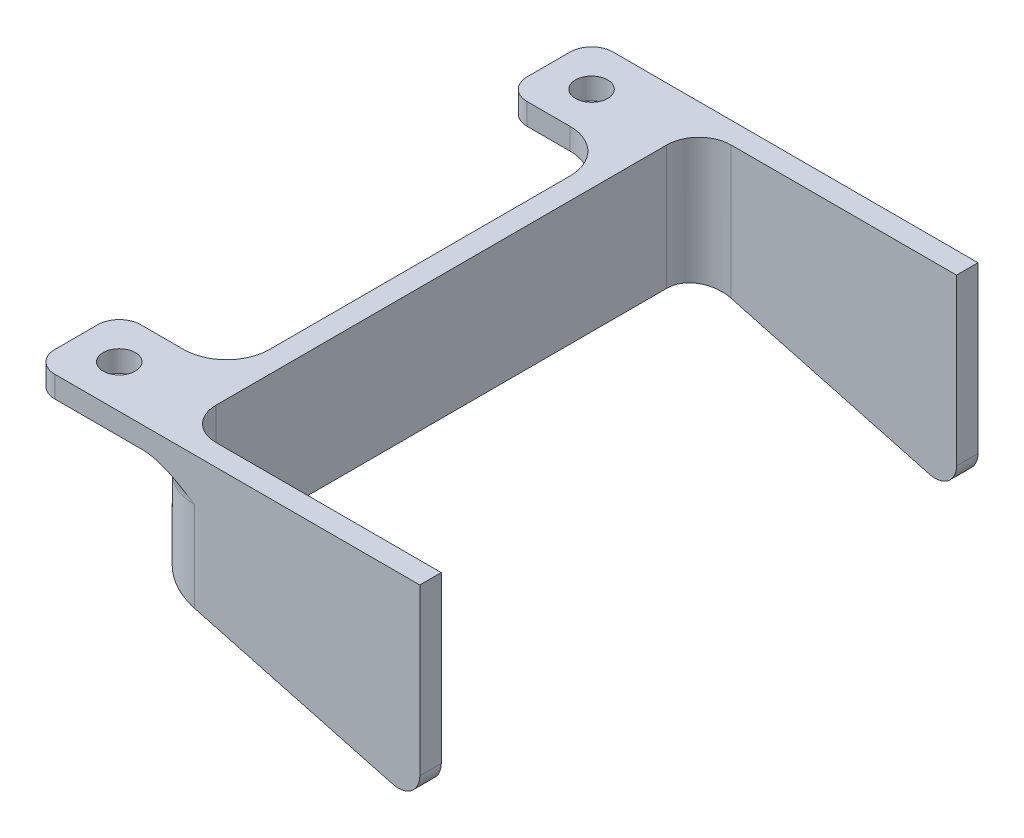
SolidWorks part; units mm, degrees
ref_plane "Front Plane" through (0, 0, 0) normal (0, 0, 1) x (1, 0, 0)
ref_plane "Top Plane" through (0, 0, 0) normal (0, 1, 0) x (1, 0, 0)
ref_plane "Right Plane" through (0, 0, 0) normal (1, 0, 0) x (0, 0, -1)
sketch "Sketch2" plane through (0, 0, 0) normal (0, 1, 0) x (1, 0, 0)
  line L0 (-6, 30) -> (6, 30)
  line L1 (6, 30) -> (6, 24)
  line L2 (6, 24) -> (2, 24)
  line L3 (2, 24) -> (2, -24)
  line L4 (2, -24) -> (6, -24)
  line L5 (6, -24) -> (6, -30)
  line L6 (6, -30) -> (-6, -30)
  line L7 (-6, -30) -> (-6, -24)
  line L8 (-6, -24) -> (-2, -24)
  line L9 (-2, -24) -> (-2, 24)
  line L10 (-2, 24) -> (-6, 24)
  line L11 (-6, 24) -> (-6, 30)
  dimension "D2" = 60
  dimension "D3" = 6
  dimension "D4" = 4
sketch "Sketch3" plane through (0, 0, 0) normal (0, 1, 0) x (1, 0, 0)
  line L5 (-8, 24) -> (-8, -24) construction
  line L6 (-8, 24) -> (-29, 24)
  line L7 (-32, 21) -> (-32, -21)
  line L8 (-29, -24) -> (-8, -24)
  line L16 (-8, 26) -> (-29, 26)
  line L17 (-34, 21) -> (-34, -21)
  line L18 (-29, -26) -> (-8, -26)
  line L19 (-8, 26) -> (-8, 24)
  line L20 (-8, -24) -> (-8, -26)
  arc A10 (-29, -24) -> (-32, -21) centre (-29, -21) cw
  arc A11 (-32, 21) -> (-29, 24) centre (-29, 21) cw
  arc A12 (-34, 21) -> (-29, 26) centre (-29, 21) cw
  arc A13 (-29, -26) -> (-34, -21) centre (-29, -21) cw
  point P2 (-8, 0)
  point P9 (-32, 24)
  dimension "D4" = 3
  dimension "D1" = 2
  dimension "D2" = 48
  dimension "D3" = 24
  dimension "D5" = 2
extrude "Boss-Extrude1" add sketch "Sketch3" along normal blind 18
sketch "Sketch4" plane through (0, 18, 0) normal (0, 1, 0) x (1, 0, 0)
  line L0 (-34, 21) -> (-34, -21) construction
  line L1 (-44, 26) -> (-29, 26)
  line L2 (-44, 26) -> (-44, 18)
  line L3 (-44, 18) -> (-34, 18)
  line L5 (-8, 26) -> (-29, 26) construction
  line L6 (-34, -18) -> (-44, -18)
  line L8 (-29, -26) -> (-44, -26)
  line L9 (-44, -18) -> (-44, -26)
  line L10 (-34, 21) -> (-34, 18)
  line L11 (-29, -26) -> (-8, -26) construction
  line L12 (-34, -18) -> (-34, -21)
  circle A0 centre (-40, 22) radius 1.5
  circle A1 centre (-40, -22) radius 1.5
  arc A2 (-29, 26) -> (-34, 21) centre (-29, 21) ccw
  arc A3 (-29, 26) -> (-34, 21) centre (-29, 21) ccw construction
  arc A4 (-29, -26) -> (-34, -21) centre (-29, -21) cw
  arc A5 (-34, -21) -> (-29, -26) centre (-29, -21) ccw construction
  point P8 (-44, 22)
  point P16 (-44, -22)
  dimension "D2" = 3
  dimension "D6" = 3
  dimension "D1" = 4
  dimension "D3" = 10
  dimension "D4" = 8
extrude "Boss-Extrude2" add sketch "Sketch4" against normal blind 2
fillet "Fillet1" radius 4 2 edges at (-34, 17, 18) (-34, 17, -18)
fillet "Fillet2" radius 2 4 edges at (-34, 16, 17.5) (-34, 16, -17.5) (-32.5355, 16, 24.5355) (-32.5355, 16, -24.5355)
fillet "Fillet3" radius 2 4 edges at (-44, 17, 26) (-44, 17, 18) (-44, 17, -18) (-44, 17, -26)
sketch "Sketch5" plane through (0, 0, 0) normal (0, 0, 1) x (1, 0, 0)
  line L0 (-8, 0) -> (-34, 6.9667)
  line L2 (-34, 6.9667) -> (-34, 0)
  line L3 (-34, 0) -> (-8, 0)
  dimension "D1" = 15
extrude "Cut-Extrude1" cut sketch "Sketch5" against normal through all both and the other way through all
fillet "Fillet4" radius 2 2 edges at (-8, 0, -25) (-8, 0, 25)
